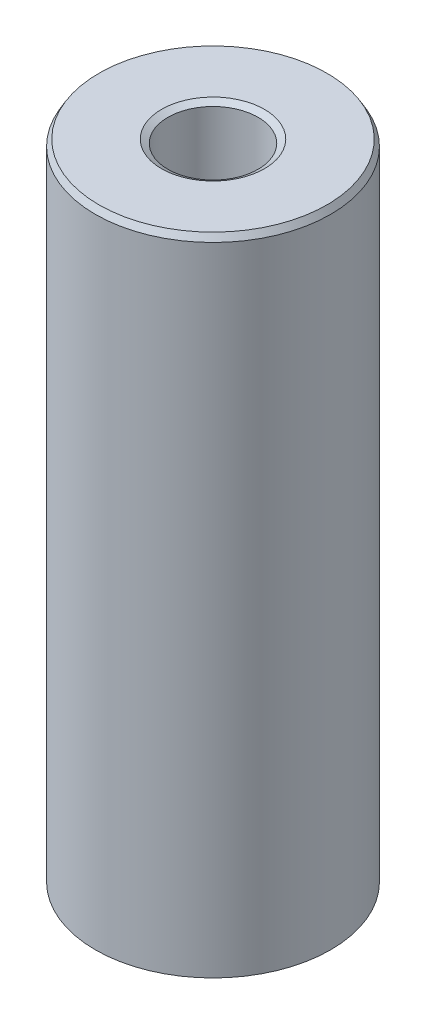
SolidWorks part; units mm, degrees
ref_plane "Front Plane" through (0, 0, 0) normal (0, 0, 1) x (1, 0, 0)
ref_plane "Top Plane" through (0, 0, 0) normal (0, 1, 0) x (1, 0, 0)
ref_plane "Right Plane" through (0, 0, 0) normal (1, 0, 0) x (0, 0, -1)
sketch "Sketch1" plane through (0, 0, 0) normal (0, 1, 0) x (1, 0, 0)
  circle A0 centre (0, 0) radius 40
  dimension "SLEEVE_OD" = 80
extrude "Boss-Extrude1" add sketch "Sketch1" along normal blind 219.8795
sketch "Sketch2" plane through (0, 0, 0) normal (0, 1, 0) x (1, 0, 0)
  circle A0 centre (0, 0) radius 15.3241
  dimension "BORE_D" = 30.6482
extrude "Cut-Extrude1" cut sketch "Sketch2" along normal through all
chamfer "Chamfer1" distance 2.1644 angle 30 4 edges at (0, 219.8795, 15.3241) (0, 0, 15.3241) (0, 0, 40) (0, 219.8795, 40) first distance on face at (0, 219.8795, 15.3241) first distance on face at (0, 0, 15.3241) first distance on face at (0, 219.8795, 40)
